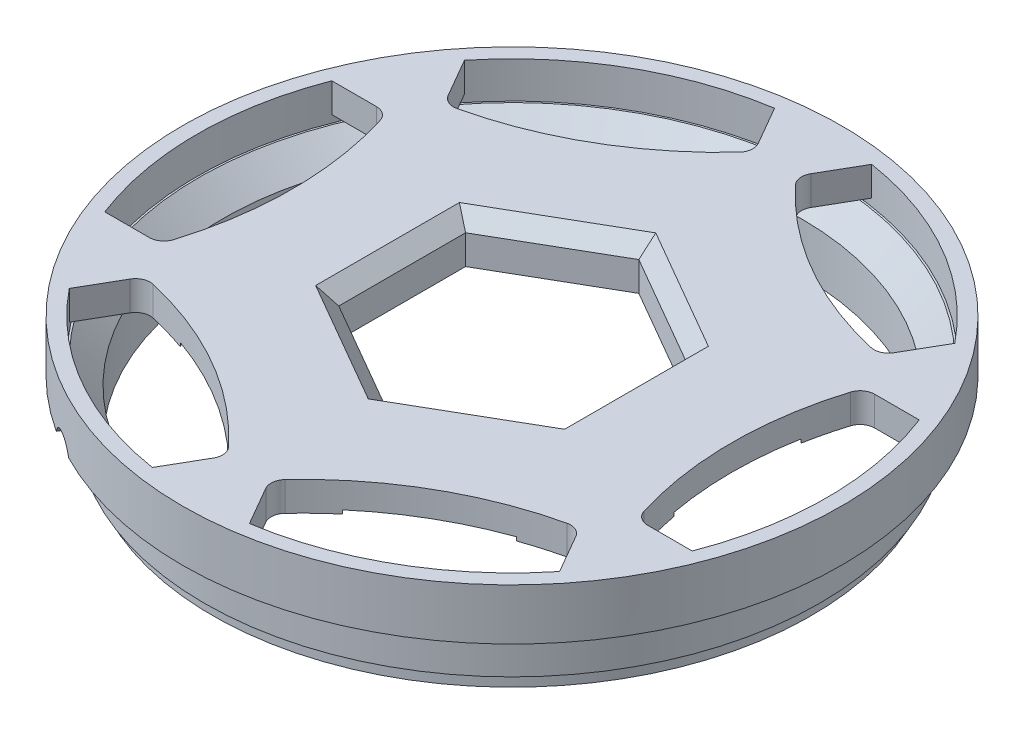
SolidWorks part; units mm, degrees
ref_plane "Ebene vorne" through (0, 0, 0) normal (0, 0, 1) x (1, 0, 0)
ref_plane "Ebene oben" through (0, 0, 0) normal (0, 1, 0) x (1, 0, 0)
ref_plane "Ebene rechts" through (0, 0, 0) normal (1, 0, 0) x (0, 0, -1)
sketch "Skizze1" plane through (0, 0, 0) normal (0, 1, 0) x (1, 0, 0)
  circle A0 centre (0, 0) radius 44
  dimension "D1" = 88
extrude "Aufsatz-Linear austragen1" add sketch "Skizze1" along normal blind 4
sketch "Skizze2" plane through (0, 4, 0) normal (0, 1, 0) x (1, 0, 0)
  line L0 (-32.5715, 15.5) -> (-71.0776, 15.5)
  line L1 (-32.5715, -15.5) -> (-71.0776, -15.5)
  line L2 (-71.0776, 15.5) -> (-71.0776, -15.5)
  circle A0 centre (-78, 0) radius 48
  circle M2 centre (0, 0) radius 44
  dimension "D1" = 78
  dimension "D2" = 96
  dimension "D3" = 31
  dimension "D4" = 15.5
extrude "Schnitt-Linear austragen2" cut sketch "Skizze2" against normal blind 10 contours L1 A0 L0 M2 region at (-36.9648, 4, 0)
sketch "Skizze4" plane through (0, 4, 0) normal (0, 1, 0) x (1, 0, 0)
  circle A0 centre (0, 0) radius 21.0071
pattern_circular "Kreismuster1" count 6 over 360 about axis through (0, 0, 0) along (0, 1, 0) of "Schnitt-Linear austragen2"
sketch "Skizze3" plane through (0, 0, 0) normal (0, -1, 0) x (1, 0, 0)
  line L1 (15, 8.6603) -> (0, 17.3205)
  line L2 (0, 17.3205) -> (-15, 8.6603)
  line L3 (-15, 8.6603) -> (-15, -8.6603)
  line L4 (-15, -8.6603) -> (0, -17.3205)
  line L5 (0, -17.3205) -> (15, -8.6603)
  line L6 (15, -8.6603) -> (15, 8.6603)
  circle A0 centre (0, 0) radius 15 construction
extrude "Schnitt-Linear austragen3" cut sketch "Skizze3" against normal blind 10 and the other way blind 4
fillet "Verrundung1" radius 2 12 edges at (-32.5715, 2, 15.5) (-2.8623, 2, 35.9577) (2.8623, 2, 35.9577) (29.7091, 2, 20.4577) (32.5715, 2, 15.5) (32.5715, 2, -15.5) (29.7091, 2, -20.4577) (2.8623, 2, -35.9577) (-2.8623, 2, -35.9577) (-29.7091, 2, -20.4577) (-32.5715, 2, -15.5) (-29.7091, 2, 20.4577)
sketch "Skizze5" plane through (13.4234, 0, 7.75) normal (-0.866, 0, -0.5) x (-0.5, 0, 0.866)
  line L0 (-34.0256, 0) -> (-41.1795, 0) construction
  circle A0 centre (-39, 0) radius 1.6
sketch "Skizze6" plane through (0, 0, -15.5) normal (0, 0, 1) x (1, 0, 0)
  line L0 (34.0256, 0) -> (41.1795, 0) construction
  circle A0 centre (39, 0) radius 1.6
sketch "Skizze7" plane through (0, 0, 0) normal (0, -1, 0) x (1, 0, 0)
  circle A0 centre (0, 0) radius 32
extrude "Schnitt-Linear austragen7" cut sketch "Skizze7" against normal blind 0.5
sketch "Skizze8" plane through (0, 4, 0) normal (0, 1, 0) x (1, 0, 0)
  circle A0 centre (0, 0) radius 45
  circle A1 centre (0, 0) radius 43
extrude "Aufsatz-Linear austragen2" add sketch "Skizze8" against normal blind 6
sketch "Skizze9" plane through (0, -2, 0) normal (0, -1, 0) x (1, 0, 0)
  circle A0 centre (0, 0) radius 45
  circle A1 centre (0, 0) radius 39.5
extrude "Aufsatz-Linear austragen3" add sketch "Skizze9" along normal blind 9 and the other way blind 1 separate body
extrude "Aufsatz-Linear austragen8" add sketch "Skizze4" against normal blind 6
chamfer "Fase1" distance 3.25 angle 45 1 edges at (0, -1, -39.5)
sketch "Skizze10" plane through (0, -11, 0) normal (0, -1, 0) x (1, 0, 0)
  circle A0 centre (0, 0) radius 42
  circle A1 centre (0, 0) radius 50
extrude "Schnitt-Linear austragen9" cut sketch "Skizze10" against normal blind 8 contours A1 | A0
sketch "Skizze11" plane through (0, -11, 0) normal (0, -1, 0) x (1, 0, 0)
  circle A0 centre (0, 0) radius 40.9
  circle A1 centre (-1.9486, 1.7726) radius 50
extrude "Schnitt-Linear austragen10" cut sketch "Skizze11" against normal blind 2
extrude "Schnitt-Linear austragen11" cut sketch "Skizze3<3>" against normal blind 6 and the other way blind 6
sketch "Skizze3<3>" plane through (0, 0, 0) normal (0, -1, 0) x (1, 0, 0) same geometry as "Skizze3"
chamfer "Fase3" distance 2 angle 45 1 edges at (0, -2, 21.0071)
chamfer "Fase5" distance 2 angle 45 6 edges at (-7.5, 4, 12.9904) (7.5, 4, 12.9904) (15, 4, 0) (7.5, 4, -12.9904) (-7.5, 4, -12.9904) (-15, 4, 0)
sketch "Skizze12" plane through (-7.5, 0, 12.9904) normal (0.5, 0, -0.866) x (-0.866, 0, -0.5)
  circle A0 centre (0, -4) radius 2.5
extrude "Schnitt-Linear austragen12" cut sketch "Skizze12" against normal through all
fillet "Verrundung2" radius 1 1 edges at (21, -3, -36.3731)
